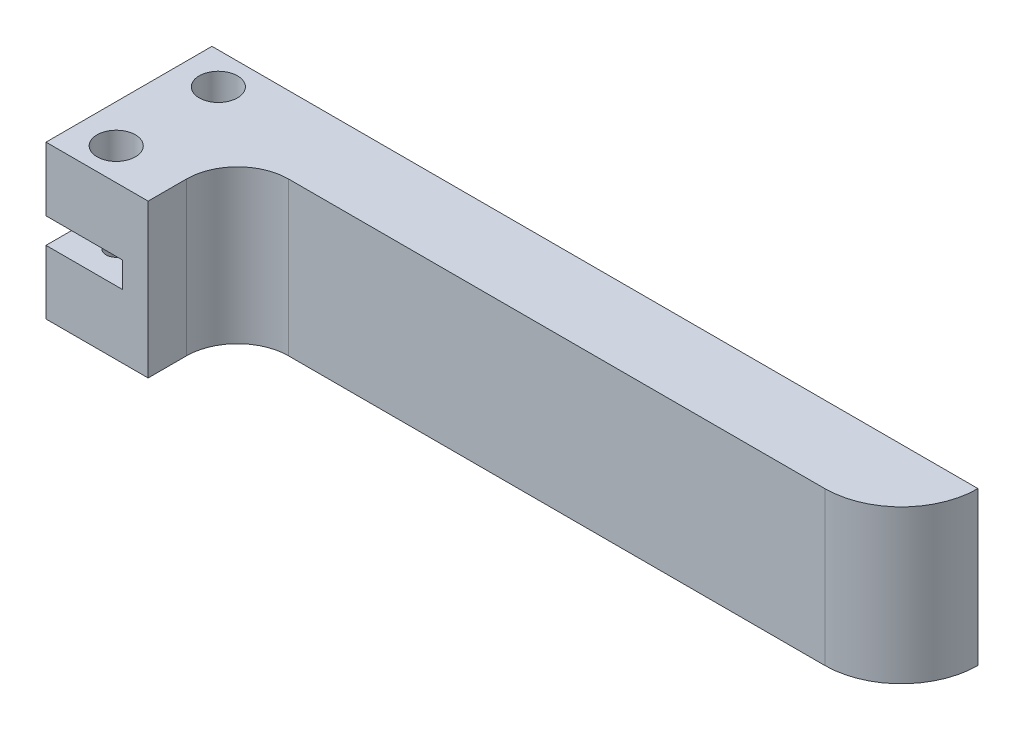
SolidWorks part; units mm, degrees
ref_plane "Front Plane" through (0, 0, 0) normal (0, 0, 1) x (1, 0, 0)
ref_plane "Top Plane" through (0, 0, 0) normal (0, 1, 0) x (1, 0, 0)
ref_plane "Right Plane" through (0, 0, 0) normal (1, 0, 0) x (0, 0, -1)
sketch "Sketch1" plane through (0, 0, 0) normal (0, 1, 0) x (1, 0, 0)
  line L1 (20, -6.5) -> (-20, -6.5)
  line L2 (20, -6.5) -> (20, 6.5)
  line L3 (20, 6.5) -> (-20, 6.5)
  line L4 (-20, -6.5) -> (-20, 6.5)
  line L5 (20, -6.5) -> (-20, 6.5) construction
  line L6 (20, 6.5) -> (-20, -6.5) construction
  point P0 (0, 0)
  dimension "D1" = 13
  dimension "D2" = 40
extrude "Boss-Extrude1" add sketch "Sketch1" along normal blind 6
sketch "Sketch2" plane through (0, 0, 6.5) normal (0, 0, 1) x (1, 0, 0)
  line L0 (-20, 6) -> (-20, 0) construction
  line L1 (-20, 4) -> (-14, 4)
  line L2 (-20, 4) -> (-20, 2)
  line L3 (-20, 2) -> (-14, 2)
  line L4 (-14, 4) -> (-14, 2)
  line L5 (-20, 0) -> (20, 0) construction
  point P6 (-20, 3)
  dimension "D1" = 2
  dimension "D2" = 6
  dimension "D3" = 3
extrude "Cut-Extrude1" cut sketch "Sketch2" against normal through all
sketch "Sketch3" plane through (0, 6, 0) normal (0, 1, 0) x (1, 0, 0)
  line L0 (-20, 6.5) -> (-20, -6.5) construction
  line L1 (20, 6.5) -> (-20, 6.5) construction
  circle A0 centre (-17, 4) radius 1.5
  circle A1 centre (-17, -4) radius 1.5
  dimension "D1" = 3
  dimension "D3" = 2.5
  dimension "D4" = 3
  dimension "D5" = 8
  dimension "D2" = 3
extrude "Cut-Extrude2" cut sketch "Sketch3" against normal blind 2
sketch "Sketch4" plane through (0, 6, 0) normal (0, 1, 0) x (1, 0, 0)
  line L1 (20, -6.5) -> (-12, -6.5)
  line L2 (20, -6.5) -> (20, 0.5)
  line L3 (20, 0.5) -> (-12, 0.5)
  line L4 (-12, -6.5) -> (-12, 0.5)
  dimension "D1" = 32
  dimension "D2" = 7
extrude "Cut-Extrude3" cut sketch "Sketch4" against normal through all
fillet "Fillet1" radius 4 1 edges at (-12, 3, -0.5)
sketch "Sketch5" plane through (0, 2, 0) normal (0, 1, 0) x (1, 0, 0)
  circle A0 centre (-17, 4) radius 0.8
  circle A1 centre (-17, -4) radius 0.8
  dimension "D1" = 1.6
  dimension "D2" = 1.6
extrude "Cut-Extrude4" cut sketch "Sketch5" against normal blind 2
sketch "Sketch6" plane through (20, 0, 0) normal (1, 0, 0) x (0, 0, -1)
  line L4 (6.5, 6) -> (0.5, 6)
  line L5 (0.5, 6) -> (0.5, 0)
  line L6 (0.5, 0) -> (6.5, 0)
  line L7 (6.5, 0) -> (6.5, 6)
  line L8 (6.5, 6) -> (0.5, 6)
  line L9 (0.5, 6) -> (0.5, 0)
  line L10 (0.5, 0) -> (6.5, 0)
  line L11 (6.5, 0) -> (6.5, 6)
  dimension "D1" = 0
extrude "Boss-Extrude2" add sketch "Sketch6" along normal blind 20
fillet "Fillet3" radius 6 1 edges at (40, 3, -0.5)
sketch "Sketch7" plane through (0, 6, 0) normal (0, 1, 0) x (1, 0, 0)
  line L5 (-8, 0.5) -> (34, 0.5)
  line L6 (40, 6.5) -> (-20, 6.5)
  line L7 (-20, 6.5) -> (-20, -6.5)
  line L8 (-20, -6.5) -> (-12, -6.5)
  line L9 (-12, -6.5) -> (-12, -3.5)
  line L10 (-8, 0.5) -> (34, 0.5)
  line L11 (40, 6.5) -> (-20, 6.5)
  line L12 (-20, 6.5) -> (-20, -6.5)
  line L13 (-20, -6.5) -> (-12, -6.5)
  line L14 (-12, -6.5) -> (-12, -3.5)
  circle A0 centre (-17, 4) radius 1.5 construction
  circle A1 centre (-17, 4) radius 1.5
  arc A2 (34, 0.5) -> (40, 6.5) centre (34, 6.5) ccw
  arc A3 (-8, 0.5) -> (-12, -3.5) centre (-8, -3.5) ccw
  arc A4 (34, 0.5) -> (40, 6.5) centre (34, 6.5) ccw
  arc A5 (-8, 0.5) -> (-12, -3.5) centre (-8, -3.5) ccw
  circle A6 centre (-17, -4) radius 1.5 construction
  circle A7 centre (-17, -4) radius 1.5
  dimension "D1" = 0
extrude "Boss-Extrude3" add sketch "Sketch7" along normal blind 3
sketch "Sketch8" plane through (0, 0, 0) normal (0, -1, 0) x (1, 0, 0)
  line L5 (-20, -6.5) -> (40, -6.5)
  line L6 (34, -0.5) -> (-8, -0.5)
  line L7 (-12, 3.5) -> (-12, 6.5)
  line L8 (-12, 6.5) -> (-20, 6.5)
  line L9 (-20, 6.5) -> (-20, -6.5)
  line L10 (-20, -6.5) -> (40, -6.5)
  line L11 (34, -0.5) -> (-8, -0.5)
  line L12 (-12, 3.5) -> (-12, 6.5)
  line L13 (-12, 6.5) -> (-20, 6.5)
  line L14 (-20, 6.5) -> (-20, -6.5)
  circle A0 centre (-17, 4) radius 0.8 construction
  circle A1 centre (-17, 4) radius 0.8
  arc A2 (40, -6.5) -> (34, -0.5) centre (34, -6.5) ccw
  arc A3 (-12, 3.5) -> (-8, -0.5) centre (-8, 3.5) ccw
  arc A4 (40, -6.5) -> (34, -0.5) centre (34, -6.5) ccw
  arc A5 (-12, 3.5) -> (-8, -0.5) centre (-8, 3.5) ccw
  circle A6 centre (-17, -4) radius 0.8 construction
  circle A7 centre (-17, -4) radius 0.8
  dimension "D1" = 0
extrude "Boss-Extrude4" add sketch "Sketch8" along normal blind 3
